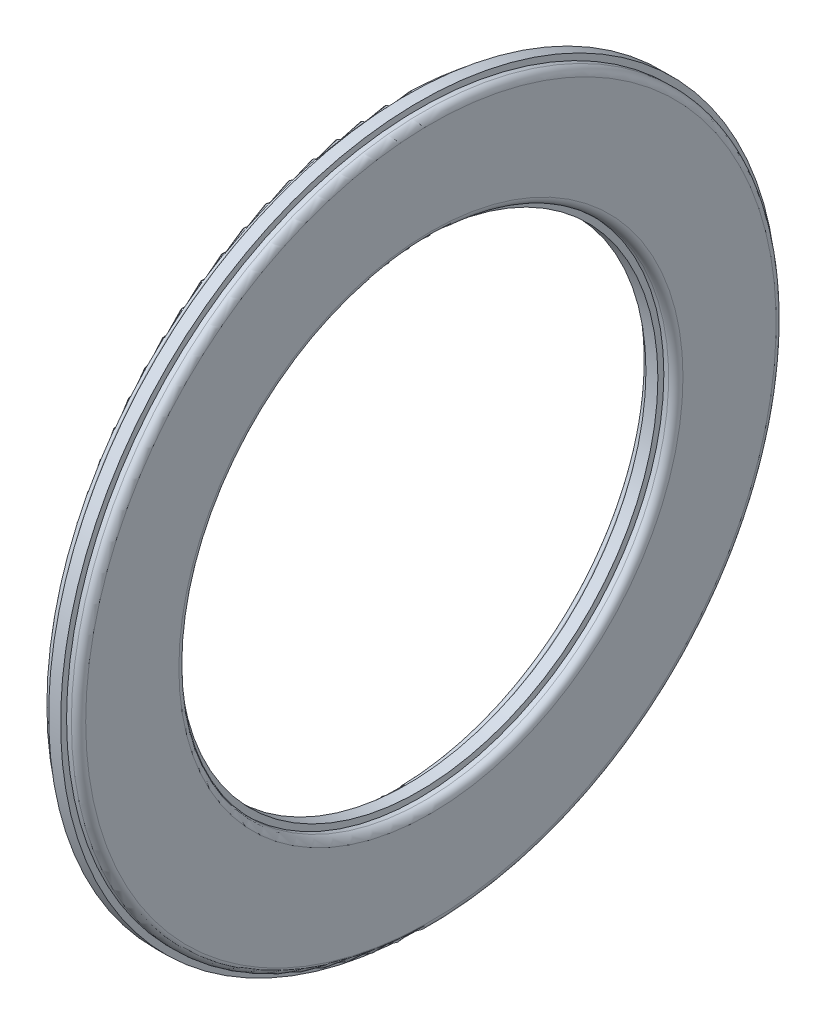
SolidWorks part; units mm, degrees
ref_plane "Plane1" through (0, 0, 0) normal (0, 0, 1) x (1, 0, 0)
ref_plane "Plane2" through (0, 0, 0) normal (0, 1, 0) x (1, 0, 0)
ref_plane "Plane3" through (0, 0, 0) normal (1, 0, 0) x (0, 0, -1)
other "Configuration Table"
sketch "Clipboard" plane through (0, 0, 0) normal (0, 0, 1) x (1, 0, 0)
  line L0 (-10, 0) -> (10, 0) construction
  line L1 (0, 0) -> (22.3471, -0.7804)
  line L2 (0, 0) -> (24.9848, 0.8725)
  line L3 (0, 0) -> (22.3471, -0.7804)
  line L4 (0, 0) -> (-22.3471, -0.7804)
  dimension "BallCLRad" = 25
sketch "CagSpiSke" plane through (0, 0, 0) normal (0, 0, 1) x (1, 0, 0)
  line L5 (-34.925, 0) -> (34.925, 0) construction
  line L6 (-0.5, 30) -> (0.5, 30)
  line L7 (-0.5, 30) -> (-0.5, 20)
  line L8 (-0.5, 20) -> (0.5, 20)
  line L9 (0.5, 30) -> (0.5, 20)
  dimension "ID" = 40
  dimension "OD" = 60
revolve "CageSpine" add sketch "CagSpiSke" angle 360 about L5 reverse direction yes
ref_axis "Axis1" through (-50, 0, 0) along (1, 0, 0)
sketch "RolDetSke" plane through (0, 0, 0) normal (0, 0, 1) x (1, 0, 0)
  line L0 (0, 33.02) -> (0, 55.88) construction
  line L3 (0, 29.5) -> (0.9, 29.5)
  line L4 (0, 29.5) -> (0, 20.5)
  line L5 (0, 20.5) -> (0.9, 20.5)
  line L6 (1.5, 28.9) -> (1.5, 21.1)
  arc A0 (1.5, 21.1) -> (0.9, 20.5) centre (0.9, 21.1) cw
  arc A1 (0.9, 29.5) -> (1.5, 28.9) centre (0.9, 28.9) cw
  dimension "offset" = 20.5
  dimension "Roller_diameter" = 3
  dimension "Cyl_Len" = 9
revolve "RollerDetailed" [suppressed] add sketch "RolDetSke" angle 360 about L0 reverse direction yes
pattern_circular "RollersDetailed" [suppressed] count 2 every 180 about axis through (-50, 0, 0) along (1, 0, 0)
sketch "RolSimSke" plane through (0, 0, 0) normal (0, 0, 1) x (1, 0, 0)
  line L1 (-17.78, 0) -> (12.7, 0) construction
  line L3 (-0.9, 29.5) -> (0.9, 29.5)
  line L4 (-1.5, 28.9) -> (-1.5, 21.1)
  line L5 (-0.9, 20.5) -> (0.9, 20.5)
  line L6 (1.5, 28.9) -> (1.5, 21.1)
  arc A0 (-1.5, 21.1) -> (-0.9, 20.5) centre (-0.9, 21.1) ccw
  arc A1 (-0.9, 29.5) -> (-1.5, 28.9) centre (-0.9, 28.9) ccw
  arc A2 (1.5, 28.9) -> (0.9, 29.5) centre (0.9, 28.9) ccw
  arc A3 (0.9, 20.5) -> (1.5, 21.1) centre (0.9, 21.1) ccw
  dimension "Halfdia" = 1.5
  dimension "offset" = 20.5
  dimension "Roller_diameter" = 3
  dimension "Cyl_Len" = 9
revolve "RollersSimplified" add sketch "RolSimSke" angle 360 about L1
equation "\"BallCLRad@Clipboard\" =  ( \"OD@CagSpiSke\" + \"ID@CagSpiSke\" )  / 4"
equation "\"offset@RolSimSke\" = \"BallCLRad@Clipboard\" - \"Cyl_Len@RolSimSke\" / 2"
equation "\"offset@RolDetSke\" = \"BallCLRad@Clipboard\" - \"Cyl_Len@RolDetSke\" / 2"
equation "\"Thickness@CagSpiSke\" =  \"Roller_diameter@RolDetSke\"  / 3"
equation "\"HalfThick@CagSpiSke\" = \"Thickness@CagSpiSke\" / 2"
equation "\"radius@RolDetSke\" =  ( \"Roller_diameter@RolDetSke\" - \"Thickness@CagSpiSke\" )  * 0.6 / 2"
equation "\"Roller_diameter@RolSimSke\" = \"Roller_diameter@RolDetSke\""
equation "\"Cyl_Len@RolSimSke\" = \"Cyl_Len@RolDetSke\""
equation "\"Rol_rad@RolSimSke\" = \"radius@RolDetSke\""
equation "\"Halfdia@RolSimSke\" = \"Roller_diameter@RolSimSke\" / 2"
equation "\"Max_count@Clipboard\" = int( 3.14159265 / atn(( \"Roller_diameter@RolDetSke\" / 2) / sqr( \"offset@RolDetSke\"  *  \"offset@RolDetSke\" - ( \"Roller_diameter@RolDetSke\" / 2) *  ( \"Roller_diameter@RolDetSke\" / 2))))"
equation "\"Max_count@Clipboard\" = ((sgn( \"Max_count@Clipboard\" - \"Count@Clipboard\" )-1)*( \"Max_count@Clipboard\" - \"Count@Clipboard\" ))/-2+ \"Count@Clipboard\""
equation "\"Count@RollersDetailed\" = int( \"Show_count@Clipboard\" ) "
equation "\"Count@RollersDetailed\" = ((sgn( \"Count@RollersDetailed\" - \"Max_count@Clipboard\" )-1)*( \"Count@RollersDetailed\" - \"Max_count@Clipboard\" ))/-2+ \"Max_count@Clipboard\""
equation "\"Count@RollersDetailed\" = ((sgn( \"Count@RollersDetailed\" - \"Min_count@Clipboard\" )+1)*( \"Count@RollersDetailed\" - \"Min_count@Clipboard\"))/2 +\"Min_count@Clipboard\""
equation "\"Angle@RollersDetailed\" = 360.0 / \"Max_count@Clipboard\""
